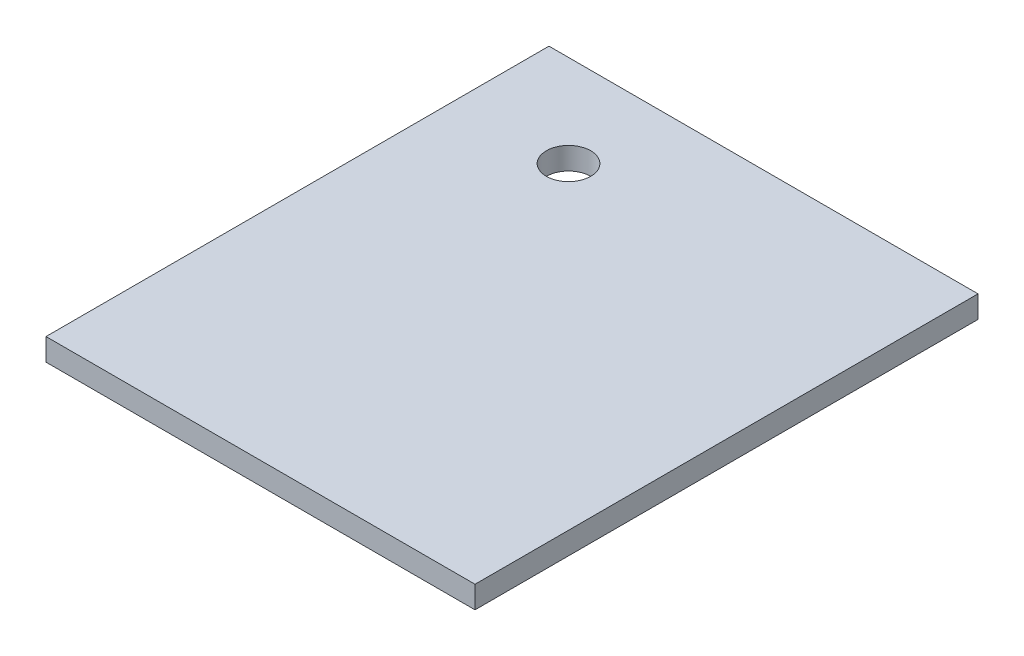
SolidWorks part; units mm, degrees
ref_plane "Front Plane" through (0, 0, 0) normal (0, 0, 1) x (1, 0, 0)
ref_plane "Top Plane" through (0, 0, 0) normal (0, 1, 0) x (1, 0, 0)
ref_plane "Right Plane" through (0, 0, 0) normal (1, 0, 0) x (0, 0, -1)
sketch "Sketch1" plane through (0, 0, 0) normal (0, 1, 0) x (1, 0, 0)
  line L1 (-26.3686, 11.4411) -> (31.6314, 11.4411)
  line L2 (-26.3686, 11.4411) -> (-26.3686, -56.5589)
  line L3 (-26.3686, -56.5589) -> (31.6314, -56.5589)
  line L4 (31.6314, 11.4411) -> (31.6314, -56.5589)
  dimension "D1" = 58
  dimension "D2" = 68
extrude "Boss-Extrude1" add sketch "Sketch1" along normal blind 3
hole_wizard "Ø6.0mm Dowel Hole1" positions "Sketch2" profile "Sketch3" hole size "Ø6.0" standard "ANSI Metric" end condition up to next
sketch "Sketch2" plane through (0, 0, 0) normal (0, -1, 0) x (-1, 0, 0)
  point P0 (11.3039, -0.9815)
sketch "Sketch3" plane through (-11.3039, 0, 0.9815) normal (1, 0, 0) x (0, 0, -1)
  line L0 (0, 0) -> (0, 3)
  line L1 (0, 3) -> (3, 3)
  line L2 (3, 3) -> (3, 0)
  line L5 (3, 0) -> (0, 0)
  line L11 (0, -6.35) -> (0, 107.95) construction
  dimension "Thru Hole Dia." = 6
  dimension "Thru Hole Depth" = 3
